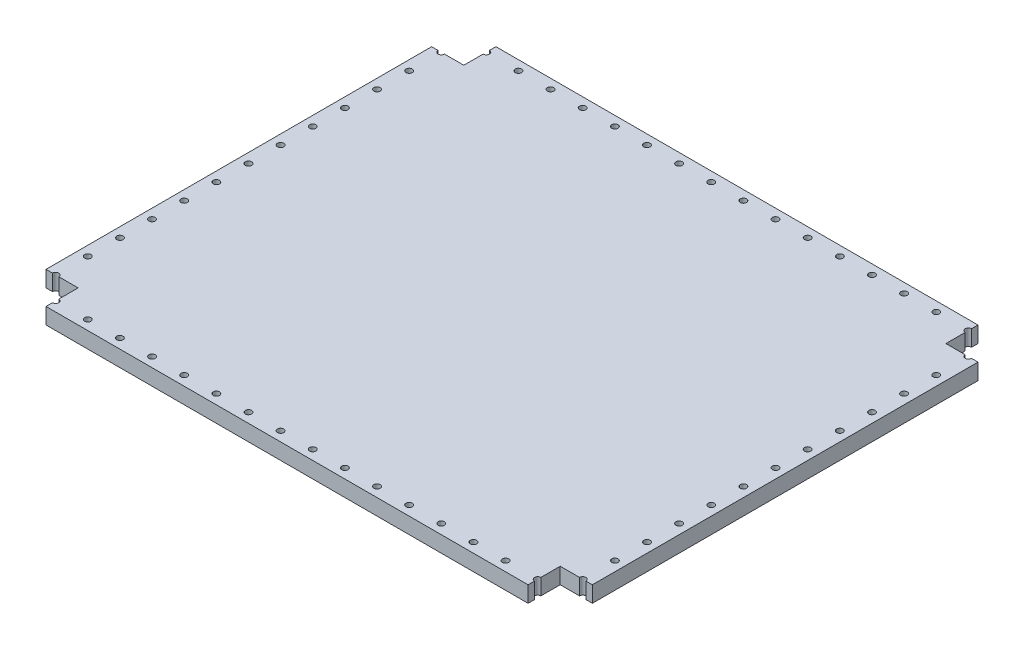
SolidWorks part; units mm, degrees
ref_plane "Front Plane" through (0, 0, 0) normal (0, 0, 1) x (1, 0, 0)
ref_plane "Top Plane" through (0, 0, 0) normal (0, 1, 0) x (1, 0, 0)
ref_plane "Right Plane" through (0, 0, 0) normal (1, 0, 0) x (0, 0, -1)
sketch "Sketch1" plane through (0, 0, 0) normal (0, 1, 0) x (1, 0, 0)
  line L1 (-215.9, -177.8) -> (215.9, -177.8)
  line L2 (-215.9, -177.8) -> (-215.9, 177.8)
  line L3 (-215.9, 177.8) -> (215.9, 177.8)
  line L4 (215.9, -177.8) -> (215.9, 177.8)
  line L5 (-215.9, -177.8) -> (215.9, 177.8) construction
  line L6 (-215.9, 177.8) -> (215.9, -177.8) construction
  point P0 (0, 0)
  dimension "D1" = 431.8
  dimension "D2" = 355.6
extrude "Boss-Extrude1" add sketch "Sketch1" along normal blind 12.7
sketch "Sketch2" plane through (0, 12.7, 0) normal (0, 1, 0) x (1, 0, 0)
  line L0 (215.9, 177.8) -> (-215.9, 177.8) construction
  line L1 (-215.9, 177.8) -> (-215.9, -177.8) construction
  circle A0 centre (-208.28, 152.4) radius 2.5
  dimension "D1" = 5
  dimension "D2" = 25.4
  dimension "D3" = 7.62
extrude "Cut-Extrude1" cut sketch "Sketch2" against normal through all
pattern_linear "LPattern1" count 13 spacing 25.4 along (0, 0, 1) of "Cut-Extrude1"
sketch "Sketch3" plane through (0, 12.7, 0) normal (0, 1, 0) x (1, 0, 0)
  line L0 (215.9, 177.8) -> (-215.9, 177.8) construction
  line L1 (-215.9, 177.8) -> (-215.9, -177.8) construction
  circle A0 centre (-190.5, 170.18) radius 2.5
  dimension "D1" = 5
  dimension "D2" = 7.62
  dimension "D3" = 25.4
extrude "Cut-Extrude2" cut sketch "Sketch3" against normal through all
pattern_linear "LPattern2" count 16 spacing 25.4 along (1, 0, 0) of "Cut-Extrude2"
sketch "Sketch4" plane through (0, 12.7, 0) normal (0, 1, 0) x (1, 0, 0)
  line L0 (215.9, -177.8) -> (215.9, 177.8) construction
  line L1 (215.9, 177.8) -> (-215.9, 177.8) construction
  circle A0 centre (208.28, 152.4) radius 2.5
  dimension "D1" = 5
  dimension "D2" = 7.62
  dimension "D3" = 25.4
extrude "Cut-Extrude3" cut sketch "Sketch4" against normal through all
pattern_linear "LPattern3" count 13 spacing 25.4 along (0, 0, 1) of "Cut-Extrude3"
sketch "Sketch5" plane through (0, 12.7, 0) normal (0, 1, 0) x (1, 0, 0)
  line L0 (215.9, -177.8) -> (215.9, 177.8) construction
  line L1 (-215.9, -177.8) -> (215.9, -177.8) construction
  circle A0 centre (190.5, -170.18) radius 2.5
  dimension "D1" = 5
  dimension "D2" = 25.4
  dimension "D3" = 7.62
extrude "Cut-Extrude4" cut sketch "Sketch5" against normal through all
pattern_linear "LPattern4" count 16 spacing 25.4 along (-1, 0, 0) of "Cut-Extrude4"
sketch "Sketch6" plane through (0, 12.7, 0) normal (0, 1, 0) x (1, 0, 0)
  line L1 (-215.9, 177.8) -> (-190.5, 177.8)
  line L2 (-215.9, 177.8) -> (-215.9, 152.4)
  line L3 (-215.9, 152.4) -> (-190.5, 152.4)
  line L4 (-190.5, 177.8) -> (-190.5, 152.4)
  dimension "D1" = 25.4
  dimension "D2" = 25.4
extrude "Cut-Extrude5" cut sketch "Sketch6" against normal through all
sketch "Sketch7" plane through (0, 12.7, 0) normal (0, 1, 0) x (1, 0, 0)
  line L1 (-215.9, -177.8) -> (-190.5, -177.8)
  line L2 (-215.9, -177.8) -> (-215.9, -152.4)
  line L3 (-215.9, -152.4) -> (-190.5, -152.4)
  line L4 (-190.5, -177.8) -> (-190.5, -152.4)
  dimension "D1" = 25.4
  dimension "D2" = 25.4
extrude "Cut-Extrude6" cut sketch "Sketch7" against normal through all
sketch "Sketch8" plane through (0, 12.7, 0) normal (0, 1, 0) x (1, 0, 0)
  line L1 (215.9, -177.8) -> (190.5, -177.8)
  line L2 (215.9, -177.8) -> (215.9, -152.4)
  line L3 (215.9, -152.4) -> (190.5, -152.4)
  line L4 (190.5, -177.8) -> (190.5, -152.4)
  dimension "D1" = 25.4
  dimension "D2" = 25.4
extrude "Cut-Extrude7" cut sketch "Sketch8" against normal through all
sketch "Sketch9" plane through (0, 12.7, 0) normal (0, 1, 0) x (1, 0, 0)
  line L1 (215.9, 177.8) -> (190.5, 177.8)
  line L2 (215.9, 177.8) -> (215.9, 152.4)
  line L3 (215.9, 152.4) -> (190.5, 152.4)
  line L4 (190.5, 177.8) -> (190.5, 152.4)
  dimension "D1" = 25.4
  dimension "D2" = 25.4
extrude "Cut-Extrude8" cut sketch "Sketch9" against normal through all
